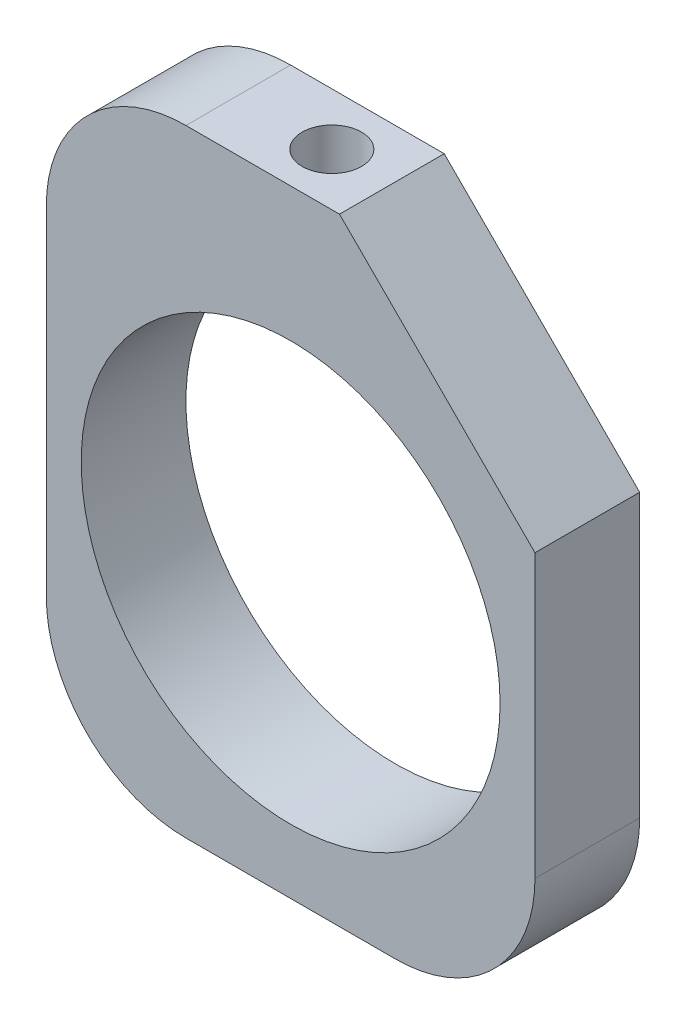
SolidWorks part; units mm, degrees
material "6063-O"
ref_plane "Front" through (0, 0, 0) normal (0, 0, 1) x (1, 0, 0)
ref_plane "Top" through (0, 0, 0) normal (0, 1, 0) x (1, 0, 0)
ref_plane "Right" through (0, 0, 0) normal (1, 0, 0) x (0, 0, -1)
sketch "Sketch1" plane through (0, 0, 0) normal (0, 0, 1) x (1, 0, 0)
  line L0 (11.1125, 12.446) -> (11.1125, 15.621)
  line L1 (4.7625, -12.446) -> (-4.7625, -12.446)
  line L2 (11.1125, -6.096) -> (11.1125, 12.446)
  line L3 (11.1125, 12.446) -> (-11.1125, 12.446)
  line L4 (-11.1125, -6.096) -> (-11.1125, 12.446)
  line L5 (11.1125, -12.446) -> (-11.1125, 12.446) construction
  line L6 (11.1125, 12.446) -> (-11.1125, -12.446) construction
  line L7 (11.1125, 15.621) -> (-4.7625, 15.621)
  line L8 (-11.1125, 9.271) -> (-11.1125, 12.446)
  circle A0 centre (0, 0) radius 9.525
  arc A1 (-11.1125, -6.096) -> (-4.7625, -12.446) centre (-4.7625, -6.096) ccw
  arc A2 (4.7625, -12.446) -> (11.1125, -6.096) centre (4.7625, -6.096) ccw
  arc A4 (-4.7625, 15.621) -> (-11.1125, 9.271) centre (-4.7625, 9.271) ccw
  point P0 (0, 0)
  point P9 (11.1125, 15.621)
  point P18 (11.1125, 15.621)
  point P21 (11.1125, 15.2844)
  dimension "D3" = 19.05
  dimension "D5" = 6.35
  dimension "D1" = 22.225
  dimension "D2" = 24.892
  dimension "D4" = 3.175
extrude "Boss-Extrude2" add sketch "Sketch1" along normal blind 4.7625 contours L7 A4 L8 L3 L0 | L1 A2 L2 L3 L4 A1 A0 region at (1.1847, 13.9772, 0) region at (10.7788, 3.175, 0)
sketch "Sketch2" plane through (0, 15.621, 0) normal (0, 1, 0) x (1, 0, 0)
  line L0 (-11.1125, -2.3813) -> (-0.508, -2.3813)
  line L1 (-11.1125, -4.7625) -> (-11.1125, 0) construction
  line L3 (11.1125, -4.7625) -> (11.1125, 0) construction
  circle A0 centre (-0.508, -2.3813) radius 1.5875
  point P6 (11.1125, -2.3813)
  dimension "D2" = 3.175
  dimension "D1" = 10.6045
hole_wizard "Tap Drill for #6-32 Tap1" positions "Sketch5" profile "Sketch4" hole size "#6-32" standard "ANSI Inch"
sketch "Sketch5" plane through (0, 15.621, 0) normal (0, 1, 0) x (1, 0, 0)
  point P0 (-0.508, -2.3813)
sketch "Sketch4" plane through (-0.508, 15.621, 2.3813) normal (1, 0, 0) x (0, 0, 1)
  line L0 (0, 0) -> (0, 19.8627)
  line L1 (0, 19.8627) -> (1.3525, 19.05)
  line L2 (1.3525, 19.05) -> (1.3525, 0)
  line L5 (1.3525, 0) -> (0, 0)
  line L10 (0, 19.8627) -> (-1.3526, 19.05) construction
  line L11 (0, -6.35) -> (0, 107.95) construction
  dimension "Hole Dia." = 2.7051
  dimension "Hole Depth" = 19.05
  dimension "Drill Angle" = 118
chamfer "Chamfer1" distance 8.89 angle 45 1 edges at (11.1125, 15.621, 2.3813)
